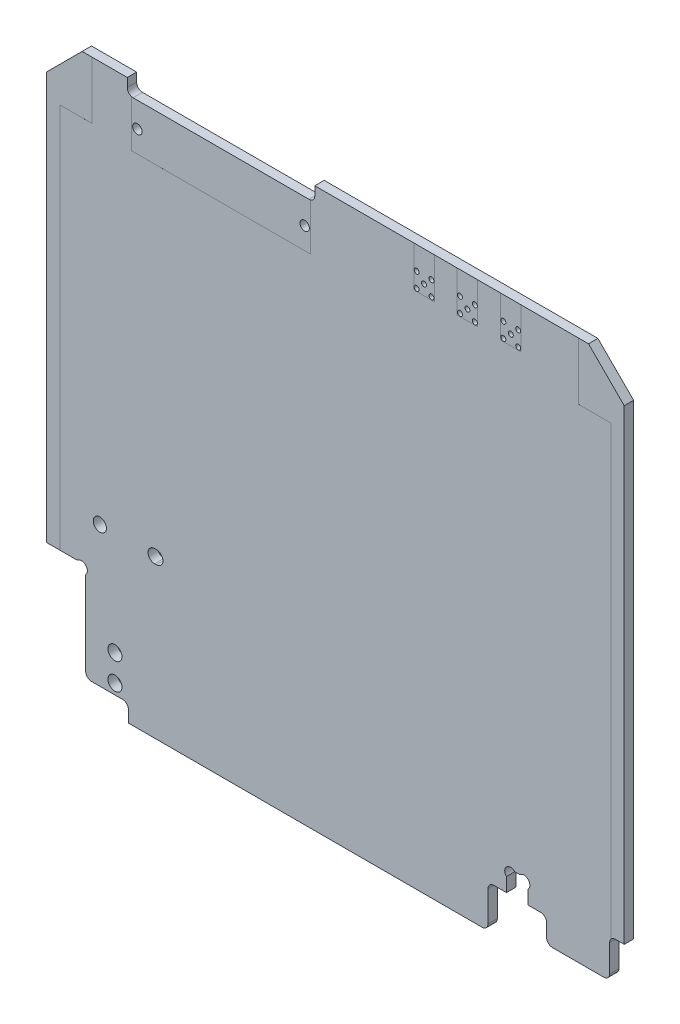
SolidWorks part; units mm, degrees
material "Oshpark board"
ref_plane "Front Plane" through (0, 0, 0) normal (0, 0, 1) x (1, 0, 0)
ref_plane "Top Plane" through (0, 0, 0) normal (0, 1, 0) x (1, 0, 0)
ref_plane "Right Plane" through (0, 0, 0) normal (1, 0, 0) x (0, 0, -1)
ref_plane "Plane4" through (0, 0, -0.0125) normal (0, 0, -1) x (-1, 0, 0)
sketch "Sketch1" plane through (0, 0, -0.0125) normal (0, 0, -1) x (-1, 0, 0)
  line L0 (35.3, -50) -> (35.3, -48)
  line L1 (36.3, -47) -> (45.8, -47)
  line L2 (46.8, -46) -> (46.8, -41.4)
  line L3 (47.8, -40.4) -> (49.3, -40.4)
  line L4 (49.3, -40.4) -> (49.3, 39.2)
  line L5 (49.3, 39.2) -> (43.2, 45.3)
  line L6 (43.2, 45.3) -> (35.5, 45.3)
  line L7 (35.5, 45.3) -> (35.5, 43.8)
  line L8 (34.5, 42.8) -> (4.5, 42.8)
  line L9 (3.5, 43.8) -> (3.5, 45.3)
  line L10 (3.5, 45.3) -> (-43.2, 45.3)
  line L11 (-43.2, 45.3) -> (-49.3, 39.2)
  line L12 (-49.3, 39.2) -> (-49.3, -40.4)
  line L13 (-49.3, -40.4) -> (-47.8, -40.4)
  line L14 (-46.8, -41.4) -> (-46.8, -46)
  line L15 (-45.8, -47) -> (-36.3, -47)
  line L16 (-35.3, -48) -> (-35.3, -50)
  line L17 (-35.3, -50) -> (35.3, -50)
  line L18 (0, -50) -> (0, 45.3) construction
  line L19 (19.5, 42.8) -> (19.5, 25.5258) construction
  line L20 (-13.87, 41.37) -> (-16.41, 38.83) construction
  line L21 (-21.27, 41.37) -> (-23.81, 38.83) construction
  line L22 (-28.67, 41.37) -> (-31.21, 38.83) construction
  arc A0 (35.3, -48) -> (36.3, -47) centre (36.3, -48) cw
  arc A1 (45.8, -47) -> (46.8, -46) centre (45.8, -46) ccw
  arc A2 (46.8, -41.4) -> (47.8, -40.4) centre (47.8, -41.4) cw
  arc A3 (35.5, 43.8) -> (34.5, 42.8) centre (34.5, 43.8) cw
  arc A4 (4.5, 42.8) -> (3.5, 43.8) centre (4.5, 43.8) cw
  arc A5 (-47.8, -40.4) -> (-46.8, -41.4) centre (-47.8, -41.4) cw
  arc A6 (-46.8, -46) -> (-45.8, -47) centre (-45.8, -46) ccw
  arc A7 (-36.3, -47) -> (-35.3, -48) centre (-36.3, -48) cw
  circle A8 centre (-21.27, 41.37) radius 0.425
  circle A9 centre (-23.81, 41.37) radius 0.425
  circle A10 centre (-22.54, 40.1) radius 0.425
  circle A11 centre (-13.87, 41.37) radius 0.425
  circle A12 centre (-23.81, 38.83) radius 0.425
  circle A13 centre (-16.41, 41.37) radius 0.425
  circle A14 centre (-15.14, 40.1) radius 0.425
  circle A15 centre (-21.27, 38.83) radius 0.425
  circle A16 centre (-28.67, 41.37) radius 0.425
  circle A17 centre (-31.21, 41.37) radius 0.425
  circle A18 centre (-16.41, 38.83) radius 0.425
  circle A19 centre (-29.94, 40.1) radius 0.425
  circle A20 centre (-31.21, 38.83) radius 0.425
  circle A21 centre (-28.67, 38.83) radius 0.425
  circle A22 centre (33.775, 38.54) radius 0.8
  circle A23 centre (5.225, 38.54) radius 0.8
  circle A24 centre (-13.87, 38.83) radius 0.425
  point P35 (-15.14, 40.1)
  dimension "D7" = 2.5
  dimension "D8" = 1.6
  dimension "D9" = 14.275
  dimension "D10" = 4.26
  dimension "D11" = 1
  dimension "D12" = 1
  dimension "D13" = 1
  dimension "D14" = 1
  dimension "D15" = 1
  dimension "D16" = 1
  dimension "D17" = 1
  dimension "D18" = 1
  dimension "D26" = 0.85
  dimension "D1" = 98.6
  dimension "D2" = 95.3
  dimension "D3" = 14
  dimension "D4" = 9.6
  dimension "D5" = 2.5
  dimension "D6" = 3
  dimension "D19" = 14
  dimension "D20" = 2.5
  dimension "D21" = 6.1
  dimension "D22" = 6.1
  dimension "D23" = 32
  dimension "D24" = 2.54
  dimension "D25" = 2.54
  dimension "D28" = 7.4
  dimension "D29" = 3.93
  dimension "D30" = 35.43
  dimension "D31" = 45
  dimension "D32" = 45
  dimension "D33" = 29.8
  dimension "D34" = 50
  dimension "D27" = 3
extrude "Boss-Extrude1" add sketch "Sketch1" against normal blind 1.6
sketch "thermalContacts_lower" plane through (0, 0, -0.0125) normal (0, 0, -1) x (-1, 0, 0)
  line L3 (47, 35.5) -> (47, -41.5)
  line L4 (41.5, 35.5) -> (41.5, 41.5)
  line L5 (41.5, 35.5) -> (47, 35.5)
  line L9 (-47, 35.5) -> (-47, -41.5)
  line L10 (-41.5, 35.5) -> (-47, 35.5)
  line L11 (-41.5, 35.5) -> (-41.5, 41.5)
  line L14 (-41.5, 41.5) -> (-41.5, 47)
  line L15 (-41.5, 41.5) -> (-49.5, 41.5) construction
  line L18 (41.5, 41.5) -> (41.5, 48.7577)
  line L19 (41.5, 41.5) -> (49.5, 41.5) construction
  line L20 (47, -41.5) -> (59.8273, -41.5)
  line L21 (59.8273, -41.5) -> (59.8273, 48.7577)
  line L22 (-56.1922, 47) -> (-41.5, 47)
  line L23 (41.5, 48.7577) -> (59.8273, 48.7577)
  line L24 (-56.1922, 47) -> (-56.1922, -41.5)
  line L25 (-47, -41.5) -> (-56.1922, -41.5)
  line L26 (43.2, 45.3) -> (35.5, 45.3) construction
  line L27 (49.3, -40.4) -> (49.3, 39.2) construction
  line L28 (-35.3, -50) -> (35.3, -50) construction
  line L29 (-49.3, 39.2) -> (-49.3, -40.4) construction
  line L30 (3.5, 45.3) -> (-43.2, 45.3) construction
  point P26 (44.0756, 48.2853)
  dimension "D1" = 9.8
  dimension "D2" = 7.8
  dimension "D3" = 2.3
  dimension "D4" = 8.5
  dimension "D5" = 8.5
  dimension "D6" = 2.3
  dimension "D7" = 7.8
  dimension "D8" = 9.8
sketch "thermalContacts_upper" plane through (0, 0, 1.5875) normal (0, 0, 1) x (1, 0, 0)
  line L3 (-47, 35.5) -> (-47, -41.5)
  line L4 (-41.5, 35.5) -> (-41.5, 41.5)
  line L5 (-41.5, 35.5) -> (-47, 35.5)
  line L9 (47, 35.5) -> (47, -41.5)
  line L10 (41.5, 35.5) -> (47, 35.5)
  line L11 (41.5, 35.5) -> (41.5, 41.5)
  line L14 (41.5, 41.5) -> (41.5, 47)
  line L15 (41.5, 41.5) -> (49.5, 41.5) construction
  line L18 (-41.5, 41.5) -> (-41.5, 47)
  line L19 (-41.5, 41.5) -> (-49.5, 41.5) construction
  line L20 (47, -41.5) -> (59.8273, -41.5)
  line L21 (59.8273, -41.5) -> (59.8273, 47)
  line L22 (59.8273, 47) -> (41.5, 47)
  line L23 (-41.5, 47) -> (-56.1922, 47)
  line L24 (-56.1922, 47) -> (-56.1922, -41.5)
  line L25 (-56.1922, -41.5) -> (-47, -41.5)
extrude "Cut-Extrude1" cut sketch "thermalContacts_lower" against normal blind 0.0001
extrude "Cut-Extrude2" cut sketch "thermalContacts_upper" against normal blind 0.0001
sketch "partFootprints" plane through (0, 0, 1.5875) normal (0, 0, 1) x (1, 0, 0)
  line L0 (-34.74, 34.84) -> (-34.74, 42.8292)
  line L1 (-4.26, 34.84) -> (-34.74, 34.84)
  line L2 (-41.5, 45.3) -> (-35.5, 45.3) construction
  line L3 (-36.1132, 45.3) -> (-39.5054, 45.3) construction
  line L4 (-4.26, 34.84) -> (-4.26, 42.8292)
  line L5 (-49.3, -40.4) -> (-49.3, 39.2) construction
  line L6 (13.39, 45.3) -> (13.39, 38.35)
  line L7 (13.39, 38.35) -> (16.89, 38.35)
  line L8 (16.89, 38.35) -> (16.89, 45.3)
  line L9 (16.89, 45.3) -> (13.39, 45.3)
  line L10 (20.79, 45.3) -> (20.79, 38.35)
  line L11 (20.79, 38.35) -> (24.29, 38.35)
  line L12 (24.29, 38.35) -> (24.29, 45.3)
  line L13 (24.29, 45.3) -> (20.79, 45.3)
  line L14 (28.19, 45.3) -> (28.19, 38.35)
  line L15 (28.19, 38.35) -> (31.69, 38.35)
  line L16 (31.69, 38.35) -> (31.69, 45.3)
  line L17 (31.69, 45.3) -> (28.19, 45.3)
  line L19 (14.12, 38.35) -> (16.16, 38.35) construction
  line L20 (-34.74, 42.8292) -> (-4.26, 42.8292)
  line L21 (-3.5, 45.3) -> (41.5, 45.3) construction
  line L22 (14.12, 38.35) -> (16.16, 38.35) construction
  line L23 (13.39, 41.85) -> (13.39, 38.35) construction
  line L24 (16.89, 41.85) -> (16.89, 38.35) construction
  line L25 (13.39, 41.85) -> (13.39, 38.35) construction
  line L26 (16.89, 41.85) -> (16.89, 38.35) construction
  arc A0 (-35.5, 43.8) -> (-34.5, 42.8) centre (-34.5, 43.8) ccw construction
  arc A1 (-4.5, 42.8) -> (-3.5, 43.8) centre (-4.5, 43.8) ccw construction
  dimension "D1" = 10.46
  dimension "D2" = 14.56
  dimension "D3" = 30.48
  dimension "D7" = 7.4
  dimension "D6" = 3
extrude "Cut-Extrude3" cut sketch "partFootprints" against normal blind 0.0001
sketch "Sketch2" plane through (0, 0, 1.5875) normal (0, 0, 1) x (1, 0, 0)
  line L0 (35.1, -50) -> (35.1, -37.5518) construction
  line L1 (35.3, -50) -> (-35.3, -50) construction
  line L2 (27, -50) -> (27, -36.9095) construction
  line L3 (35.3, -48) -> (35.3, -50) construction
  line L4 (29.2, -42.8) -> (29.2, -40.4142)
  line L5 (27, -39) -> (35.1, -39) construction
  line L6 (30.6142, -39) -> (31.4858, -39)
  line L7 (32.9, -40.4142) -> (32.9, -42.8)
  line L8 (26.05, -50) -> (36.05, -50)
  line L9 (30.6142, -39) -> (31.4858, -39) construction
  line L10 (26.05, -50) -> (26.05, -42.8)
  line L11 (26.05, -42.8) -> (29.2, -42.8)
  line L12 (31.05, -39) -> (31.05, -50) construction
  line L13 (36.05, -42.8) -> (32.9, -42.8)
  line L14 (36.05, -50) -> (36.05, -42.8)
  line L15 (48.0683, 27.2) -> (36.7758, 27.2) construction
  line L16 (48.0683, 35.5) -> (35.6387, 35.5) construction
  line L17 (42.1, 29.55) -> (39.0071, 29.55) construction
  line L18 (38.3, 35.5) -> (38.3, 27.2) construction
  line L19 (38.3, 30.2571) -> (38.3, 32.4429) construction
  line L20 (39.0071, 33.15) -> (42.1, 33.15) construction
  line L21 (49.3, 29.1) -> (49.3, 33.6) construction
  line L22 (38.3, 30.2571) -> (38.3, 32.4429) construction
  line L23 (49.3, 29.1) -> (42.1, 29.1) construction
  line L24 (42.1, 29.1) -> (42.1, 29.55) construction
  line L25 (38.3, 31.35) -> (49.3, 31.35) construction
  line L26 (42.1, 33.6) -> (42.1, 33.15) construction
  line L27 (49.3, 33.6) -> (42.1, 33.6) construction
  line L28 (49.3, -40.4) -> (49.3, 39.2) construction
  line L30 (31.69, 45.3) -> (41.5, 45.3) construction
  arc A0 (29.2, -40.4142) -> (30.6142, -39) centre (29.9071, -39.7071) cw
  arc A1 (31.4858, -39) -> (32.9, -40.4142) centre (32.1929, -39.7071) cw
  arc A2 (39.0071, 29.55) -> (38.3, 30.2571) centre (38.6536, 29.9036) cw construction
  arc A3 (38.3, 32.4429) -> (39.0071, 33.15) centre (38.6536, 32.7964) cw construction
  point P8 (35.3, -49)
  point P39 (38.3, 31.35)
  point P46 (38.3, 31.35)
  point P47 (38.3, 29.55)
  point P48 (38.3, 33.15)
  point P57 (31.05, -39)
  point P59 (32.9, -39)
  point P60 (29.2, -39)
  dimension "D5" = 1
  dimension "D8" = 0.5
  dimension "D1" = 0.2
  dimension "D2" = 8.3
  dimension "D3" = 3.7
  dimension "D4" = 11
  dimension "D6" = 3.8
  dimension "D7" = 10
  dimension "D9" = 3.6
  dimension "D10" = 11
  dimension "D11" = 3.8
  dimension "D12" = 4.5
  dimension "D13" = 9.8
  dimension "D14" = 8.3
extrude "Cut-Extrude4" cut sketch "Sketch2" against normal through all
sketch "Sketch3" plane through (0, 0, 1.5875) normal (0, 0, 1) x (1, 0, 0)
  line L0 (45.8, -47) -> (36.3, -47) construction
  line L1 (31.741, -47) -> (39.5208, -47)
  line L2 (31.741, -47) -> (31.741, -52.1552)
  line L3 (31.741, -52.1552) -> (39.5208, -52.1552)
  line L4 (39.5208, -47) -> (39.5208, -52.1552)
extrude "Cut-Extrude5" cut sketch "Sketch3" against normal blind 10
fillet "Fillet1" radius 1 4 edges at (36.05, -42.8, 0.7875) (26.05, -42.8, 0.7875) (36.05, -47, 0.7875) (26.05, -50, 0.7875)
sketch "Sketch4" plane through (0, 0, 1.5875) normal (0, 0, 1) x (1, 0, 0)
  line L0 (-36.3, -47) -> (-45.8, -47) construction
  line L1 (-51.3808, -30.3) -> (-44.0142, -30.3)
  line L2 (-51.3808, -30.3) -> (-51.3808, -47)
  line L3 (-51.3808, -47) -> (-42.6, -47)
  line L4 (-42.6, -31.7142) -> (-42.6, -47)
  line L5 (-42.8, -37.156) -> (-42.8, -48.7489) construction
  line L6 (-44.0142, -30.3) -> (-42.6, -30.3) construction
  line L7 (-42.6, -30.3) -> (-42.6, -31.7142) construction
  arc A0 (-44.0142, -30.3) -> (-42.6, -31.7142) centre (-43.3071, -31.0071) cw
  point P11 (-42.6, -30.3)
  dimension "D1" = 1
  dimension "D2" = 0.2
  dimension "D3" = 16.7
extrude "Cut-Extrude6" cut sketch "Sketch4" against normal through all
fillet "Fillet2" radius 1 1 edges at (-42.6, -47, 0.7875)
sketch "Sketch5" plane through (0, 0, 1.5875) normal (0, 0, 1) x (1, 0, 0)
  line L0 (-30.525, -24.225) -> (-30.825, -24.225) construction
  line L1 (-30.525, -24.225) -> (-30.825, -24.225)
  line L2 (-30.825, -21.975) -> (-30.525, -21.975) construction
  line L3 (-30.825, -21.975) -> (-30.525, -21.975)
  circle A0 centre (-40.175, -23.1) radius 1.125 construction
  circle A1 centre (-40.175, -23.1) radius 1.125
  arc A2 (-30.825, -21.975) -> (-30.825, -24.225) centre (-30.825, -23.1) ccw construction
  arc A3 (-30.525, -24.225) -> (-30.525, -21.975) centre (-30.525, -23.1) ccw construction
  arc A4 (-30.825, -21.975) -> (-30.825, -24.225) centre (-30.825, -23.1) ccw
  arc A5 (-30.525, -24.225) -> (-30.525, -21.975) centre (-30.525, -23.1) ccw
extrude "Cut-Extrude7" cut sketch "Sketch5" against normal through all
sketch "Sketch6" plane through (0, 0, 1.5875) normal (0, 0, 1) x (1, 0, 0)
  circle A1 centre (-37.6, -40.75) radius 1.2
  circle A2 centre (-37.6, -45.25) radius 1.2 construction
  circle A3 centre (-37.6, -45.25) radius 1.2
  circle A4 centre (-37.6, -40.75) radius 1.2 construction
extrude "Cut-Extrude8" cut sketch "Sketch6" against normal through all
